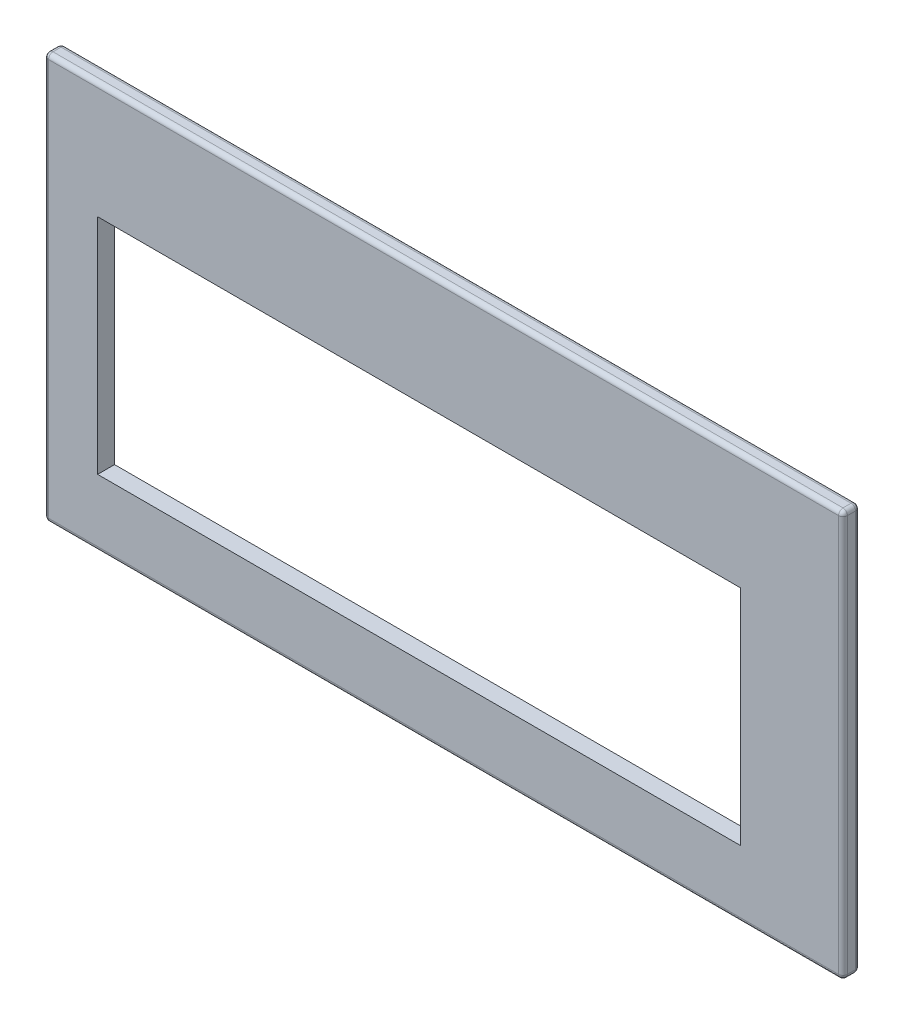
SolidWorks part; units mm, degrees
ref_plane "Front Plane" through (0, 0, 0) normal (0, 0, 1) x (1, 0, 0)
ref_plane "Top Plane" through (0, 0, 0) normal (0, 1, 0) x (1, 0, 0)
ref_plane "Right Plane" through (0, 0, 0) normal (1, 0, 0) x (0, 0, -1)
sketch "Sketch1" plane through (0, 0, 0) normal (0, 0, 1) x (1, 0, 0)
  line L1 (-67.1123, 13.7449) -> (22.3877, 13.7449)
  line L2 (-67.1123, 13.7449) -> (-67.1123, -31.7551)
  line L3 (-67.1123, -31.7551) -> (22.3877, -31.7551)
  line L4 (22.3877, 13.7449) -> (22.3877, -31.7551)
extrude "Boss-Extrude1" add sketch "Sketch1" along normal blind 1.9
fillet "Fillet1" radius 0.5 10 edges at (22.3877, -31.7551, 0.95) (22.3877, -9.0051, 1.9) (22.3877, -9.0051, 0) (22.3877, 13.7449, 0.95) (-22.3623, 13.7449, 1.9) (-22.3623, 13.7449, 0) (-67.1123, 13.7449, 0.95) (-67.1123, -9.0051, 1.9) (-67.1123, -31.7551, 0.95) (-67.1123, -9.0051, 0)
fillet "Fillet2" radius 0.5 6 edges at (-66.9659, -31.6087, 1.7536) (22.2413, -31.6087, 1.7536) (-66.9659, -31.6087, 0.1464) (22.2413, -31.6087, 0.1464) (-22.3623, -31.7551, 1.9) (-22.3623, -31.7551, 0)
sketch "Sketch2" plane through (0, 0, 1.9) normal (0, 0, 1) x (1, 0, 0)
  line L0 (-67.1123, -31.2551) -> (-67.1123, 13.2449) construction
  line L1 (-61.1123, 0.7449) -> (10.8877, 0.7449)
  line L2 (-61.1123, 0.7449) -> (-61.1123, -24.2551)
  line L3 (-61.1123, -24.2551) -> (10.8877, -24.2551)
  line L4 (10.8877, 0.7449) -> (10.8877, -24.2551)
  line L5 (21.8877, -31.7551) -> (-66.6123, -31.7551) construction
  dimension "D1" = 25
  dimension "D2" = 72
  dimension "D3" = 6
  dimension "D4" = 7.5
extrude "Cut-Extrude1" cut sketch "Sketch2" against normal through all both and the other way through all
